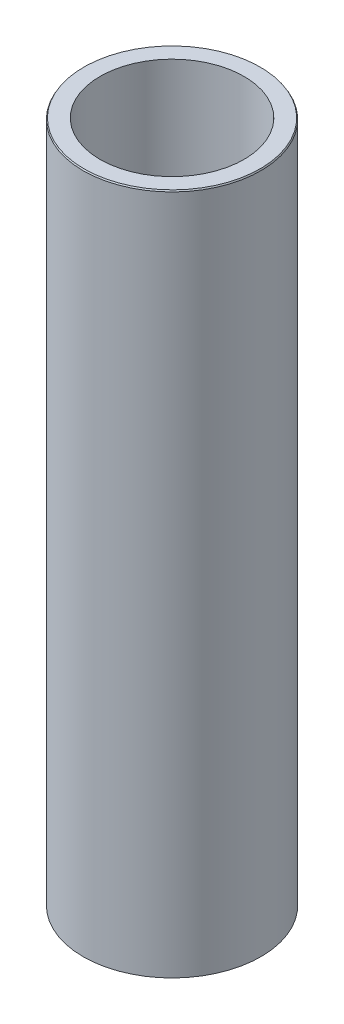
SolidWorks part; units mm, degrees
ref_plane "Front Plane" through (0, 0, 0) normal (0, 0, 1) x (1, 0, 0)
ref_plane "Top Plane" through (0, 0, 0) normal (0, 1, 0) x (1, 0, 0)
ref_plane "Right Plane" through (0, 0, 0) normal (1, 0, 0) x (0, 0, -1)
sketch "Sketch1" plane through (0, 0, 0) normal (0, 1, 0) x (1, 0, 0)
  circle A0 centre (0, 0) radius 57.5
  dimension "SHAFT_OD" = 115
extrude "Boss-Extrude1" add sketch "Sketch1" along normal blind 441.6582
sketch "Sketch2" plane through (0, 0, 0) normal (0, 1, 0) x (1, 0, 0)
  circle A0 centre (0, 0) radius 46.5658
  dimension "BORE_D" = 93.1316
extrude "Cut-Extrude1" cut sketch "Sketch2" along normal through all
chamfer "Chamfer1" distance 0.8388 angle 30 2 edges at (0, 441.6582, 57.5) (0, 0, 57.5) first distance on face at (0, 441.6582, 57.5) first distance on face at (0, 0, 46.5658)
